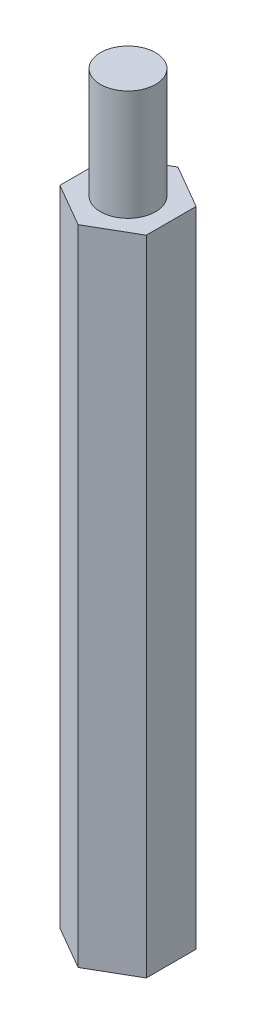
SolidWorks part; units mm, degrees
ref_plane "Front Plane" through (0, 0, 0) normal (0, 0, 1) x (1, 0, 0)
ref_plane "Top Plane" through (0, 0, 0) normal (0, 1, 0) x (1, 0, 0)
ref_plane "Right Plane" through (0, 0, 0) normal (1, 0, 0) x (0, 0, -1)
sketch "Sketch1" plane through (0, 0, 0) normal (0, 1, 0) x (1, 0, 0)
  line L1 (0, 2.7135) -> (-2.35, 1.3568)
  line L2 (-2.35, 1.3568) -> (-2.35, -1.3568)
  line L3 (-2.35, -1.3568) -> (0, -2.7135)
  line L4 (0, -2.7135) -> (2.35, -1.3568)
  line L5 (2.35, -1.3568) -> (2.35, 1.3568)
  line L6 (2.35, 1.3568) -> (0, 2.7135)
  circle A0 centre (0, 0) radius 2.35 construction
  dimension "D1" = 4.7
extrude "Boss-Extrude1" add sketch "Sketch1" along normal blind 35
sketch "Sketch2" plane through (0, 35, 0) normal (0, 1, 0) x (1, 0, 0)
  circle A0 centre (0, 0) radius 1.5
  dimension "D1" = 3
extrude "Boss-Extrude2" add sketch "Sketch2" along normal blind 6
sketch "Sketch5" plane through (0, 0, 0) normal (0, -1, 0) x (1, 0, 0)
  circle A0 centre (0, 0) radius 1.5
  dimension "D1" = 3
extrude "Cut-Extrude1" cut sketch "Sketch5" against normal blind 6
